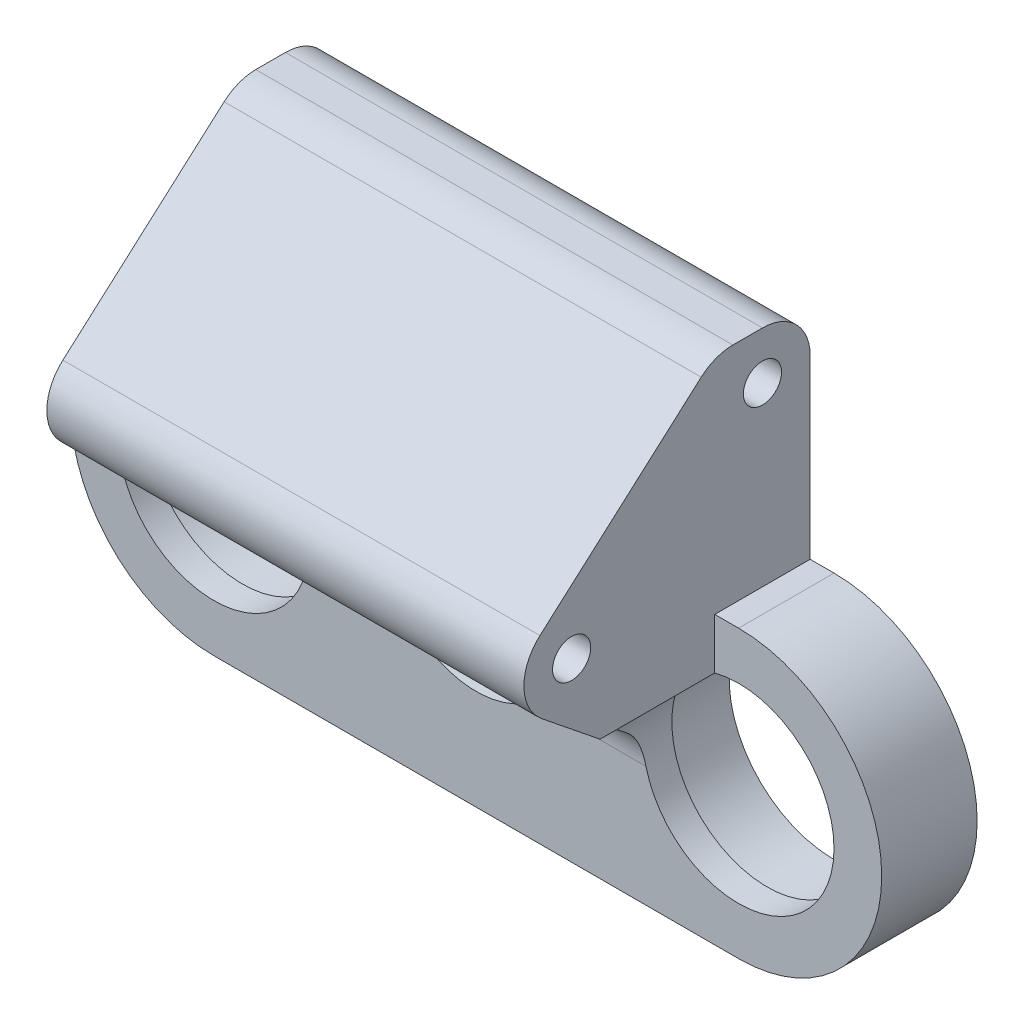
SolidWorks part; units mm, degrees
ref_plane "Plan de face" through (0, 0, 0) normal (0, 0, 1) x (1, 0, 0)
ref_plane "Plan de dessus" through (0, 0, 0) normal (0, 1, 0) x (1, 0, 0)
ref_plane "Plan de droite" through (0, 0, 0) normal (1, 0, 0) x (0, 0, -1)
sketch "Sketch1" plane through (0, 0, 0) normal (0, 0, 1) x (1, 0, 0)
  line L0 (27.5, 0) -> (-27.5, 0) construction
  line L1 (27.5, -15) -> (-27.5, -15)
  line L2 (27.5, 15) -> (-27.5, 15)
  line L3 (0, 5) -> (0, 0) construction
  arc A0 (27.5, -15) -> (27.5, 15) centre (27.5, 0) ccw
  arc A1 (-27.5, 15) -> (-27.5, -15) centre (-27.5, 0) ccw
  circle A2 centre (-27.5, 0) radius 11
  circle A3 centre (27.5, 0) radius 11
  circle A5 centre (0, 5) radius 9.5
  circle A6 centre (0, 5) radius 13.5
  point P2 (0, 0)
  dimension "D1" = 22
  dimension "D2" = 22
  dimension "D3" = 19
  dimension "D4" = 30
  dimension "D7" = 4
  dimension "D5" = 55
  dimension "D6" = 5
extrude "Boss-Extrude1" add sketch "Sketch1" along normal blind 10 contours L2 A6 A5 | A6 L2 A1 L1 A0 A3 A2 | L2 A6 region at (0, -14.0986, 0) region at (12.0154, 10.3238, 0) region at (0, 16.4168, 0)
sketch "Sketch2" plane through (0, 0, 10) normal (0, 0, 1) x (1, 0, 0)
  circle A0 centre (-27.5, 0) radius 11
  circle A2 centre (27.5, 0) radius 11
  circle A6 centre (-27.5, 0) radius 10
  circle A8 centre (27.5, 0) radius 10
  circle A9 centre (-27.5, 0) radius 11 construction
  circle A10 centre (27.5, 0) radius 11 construction
  dimension "D1" = 1
  dimension "D3" = 1
extrude "Boss-Extrude2" add sketch "Sketch2" against normal blind 3
sketch "Sketch4" plane through (0, 0, 0) normal (0, 0, -1) x (-1, 0, 0)
  circle A0 centre (0, 5) radius 9.5
  circle A1 centre (0, 5) radius 8.5
  circle A3 centre (0, 5) radius 9.5 construction
  dimension "D1" = 1
extrude "Boss-Extrude3" add sketch "Sketch4" against normal blind 4
sketch "Sketch5" plane through (0, 0, 0) normal (1, 0, 0) x (0, 0, -1)
  line L0 (0, 18.5) -> (0, 38.5)
  line L1 (0, 38.5) -> (-10, 38.5)
  line L2 (-10, 38.5) -> (-32.7411, 18.3144)
  line L3 (-32.7411, 18.3144) -> (-10, 0)
  line L4 (0, 15) -> (0, 18.5)
  line L5 (0, 15) -> (-10, 15)
  line L6 (-10, 15) -> (-10, 0)
  line L7 (-10, 15) -> (-10, -15) construction
  line L8 (-5, 33.5) -> (-5, 38.5) construction
  line L9 (-25, 18.5) -> (-28.3192, 22.2394) construction
  line L10 (-28.1361, 14.6058) -> (-25, 18.5) construction
  circle A0 centre (-5, 33.5) radius 2
  circle A1 centre (-25, 18.5) radius 2
  dimension "D5" = 4
  dimension "D9" = 4
  dimension "D1" = 10
  dimension "D2" = 5
  dimension "D3" = 20
  dimension "D4" = 5
  dimension "D6" = 15
  dimension "D7" = 20
  dimension "D8" = 5
extrude "Boss-Extrude4" add sketch "Sketch5" along normal mid plane 50 contours A1 | A0 | L6 L3 L2 L1 L0 L4 L5 region at (0, 33.5, 5) region at (0, 18.5, 25)
fillet "Fillet1" radius 5 3 edges at (0, 18.3144, 32.7411) (0, 38.5, 10) (0, 38.5, 0)
sketch "Sketch6" plane through (0, 0, 10) normal (0, 0, -1) x (-1, 0, 0)
  circle A0 centre (-27.5, 0) radius 10
  circle A1 centre (0, 5) radius 9.5
  circle A2 centre (27.5, 0) radius 10
  circle A3 centre (-27.5, 0) radius 10 construction
  arc A4 (8.0777, 0) -> (-8.0777, 0) centre (0, 5) ccw construction
  arc A5 (17.5, 0) -> (25, 9.6825) centre (27.5, 0) ccw construction
extrude "Cut-Extrude1" cut sketch "Sketch6" against normal blind 50
fillet "Fillet2" radius 5 2 edges at (12.7889, 0, 10) (-12.7889, 0, 10)
